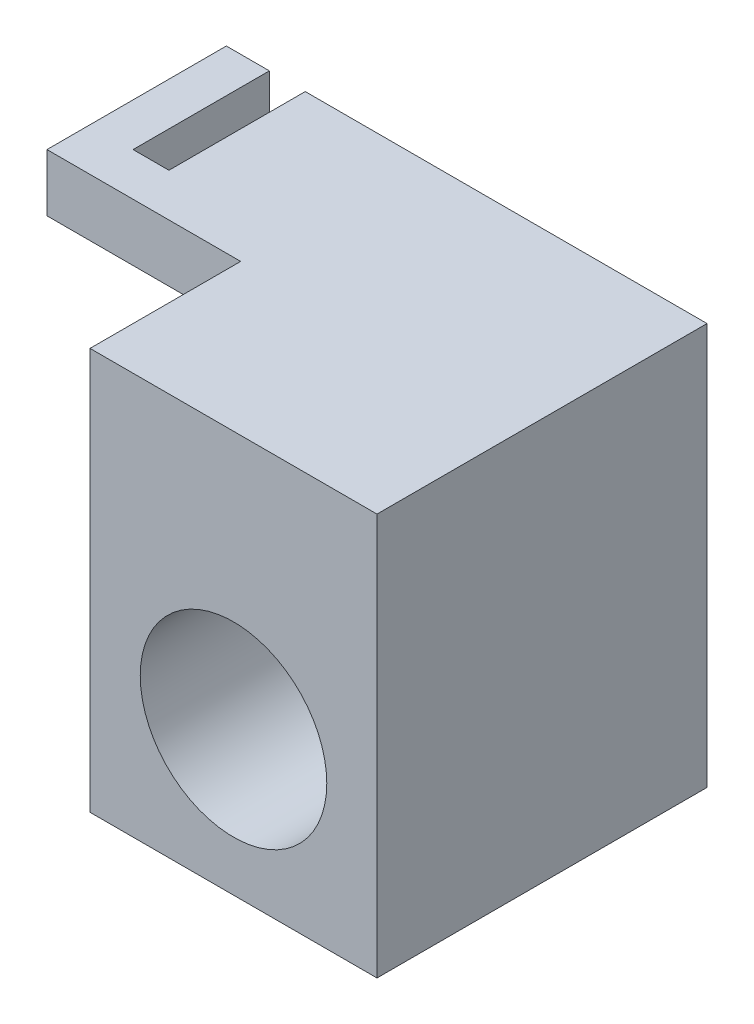
SolidWorks part; units mm, degrees
ref_plane "Front Plane" through (0, 0, 0) normal (0, 0, 1) x (1, 0, 0)
ref_plane "Top Plane" through (0, 0, 0) normal (0, 1, 0) x (1, 0, 0)
ref_plane "Right Plane" through (0, 0, 0) normal (1, 0, 0) x (0, 0, -1)
sketch "Sketch1" plane through (0, 0, 0) normal (0, 0, 1) x (1, 0, 0)
  line L1 (0, 0) -> (-20, 0)
  line L2 (0, 0) -> (0, -28)
  line L3 (0, -28) -> (-20, -28)
  line L4 (-20, 0) -> (-20, -28)
  dimension "D1" = 20
  dimension "D2" = 28
extrude "Boss-Extrude1" add sketch "Sketch1" along normal blind 23
sketch "Sketch2" plane through (0, 0, 23) normal (0, 0, 1) x (1, 0, 0)
  line L0 (-20, 0) -> (-20, -28) construction
  line L1 (0, 0) -> (-20, 0) construction
  circle A0 centre (-10, -18) radius 6.5
  point P4 (-20, -14)
  point P7 (-10, 0)
  dimension "D1" = 4
  dimension "D2" = 0
  dimension "D3" = 13
extrude "Cut-Extrude1" cut sketch "Sketch2" against normal blind 40
sketch "Sketch3" plane through (-20, 0, 0) normal (-1, 0, 0) x (0, 0, 1)
  line L1 (0, 0) -> (0, -28) construction
  circle A0 centre (8, -18) radius 2.75
  point P7 (0, -14)
  dimension "D1" = 8
  dimension "D2" = 4
  dimension "D3" = 5.5
extrude "Cut-Extrude2" cut sketch "Sketch3" against normal blind 10
thread "Thread1" pitch 2.1167 method cut profile "Thread Profile1" start angle 0, offset 0, length 10, pitch 2.1167, diameter 5.5
ref_plane "Plane1" through (-20, -18, 5.25) normal (0, -1, 0) x (0, 0, -1)
sketch "Thread Profile1" plane through (-20, -18, 5.25) normal (0, -1, 0) x (0, 0, -1)
  line L0 (0, 0) -> (0, 2.1167) construction
  line L1 (0, 0) -> (1.1457, 0.6615)
  line L2 (1.1457, 0.6615) -> (1.1457, 0.926)
  line L3 (1.1457, 0.926) -> (0, 1.5875)
  line L4 (1.1457, 0.7937) -> (0, 0.7937) construction
  line L11 (0, 0) -> (0, 1.5875)
  point P2 (0, 0)
  dimension "Pitch" = 2.1167
  dimension "Profile_Angle" = 60
  dimension "Profile_Land" = 0.2646
  dimension "Profile_Height" = 1.1457
sketch "Sketch6" plane through (-20, 0, 0) normal (-1, 0, 0) x (0, 0, 1)
  circle A0 centre (8, -18) radius 3.75
  dimension "D1" = 7.5
extrude "Cut-Extrude3" cut sketch "Sketch6" against normal blind 1
sketch "Sketch7" plane through (-20, 0, 0) normal (-1, 0, 0) x (0, 0, 1)
  line L0 (23, 0) -> (0, 0) construction
  line L1 (0, -4) -> (12.5, -4)
  line L2 (0, -4) -> (0, 0)
  line L3 (0, 0) -> (12.5, 0)
  line L4 (12.5, -4) -> (12.5, 0)
  line L5 (0, 0) -> (0, -28) construction
  dimension "D1" = 0
  dimension "D2" = 0
  dimension "D3" = 4
  dimension "D4" = 12.5
extrude "Boss-Extrude2" add sketch "Sketch7" along normal blind 13.5
sketch "Sketch8" plane through (0, -4, 0) normal (0, -1, 0) x (-1, 0, 0)
  line L0 (33.5, 0) -> (20, 0) construction
  line L1 (30.5, 0) -> (28, 0)
  line L2 (30.5, 0) -> (30.5, -9.5)
  line L3 (30.5, -9.5) -> (28, -9.5)
  line L4 (28, 0) -> (28, -9.5)
  line L5 (33.5, 0) -> (33.5, -12.5) construction
  dimension "D1" = 9.5
  dimension "D2" = 3
  dimension "D3" = 2.5
extrude "Cut-Extrude4" cut sketch "Sketch8" against normal blind 10
